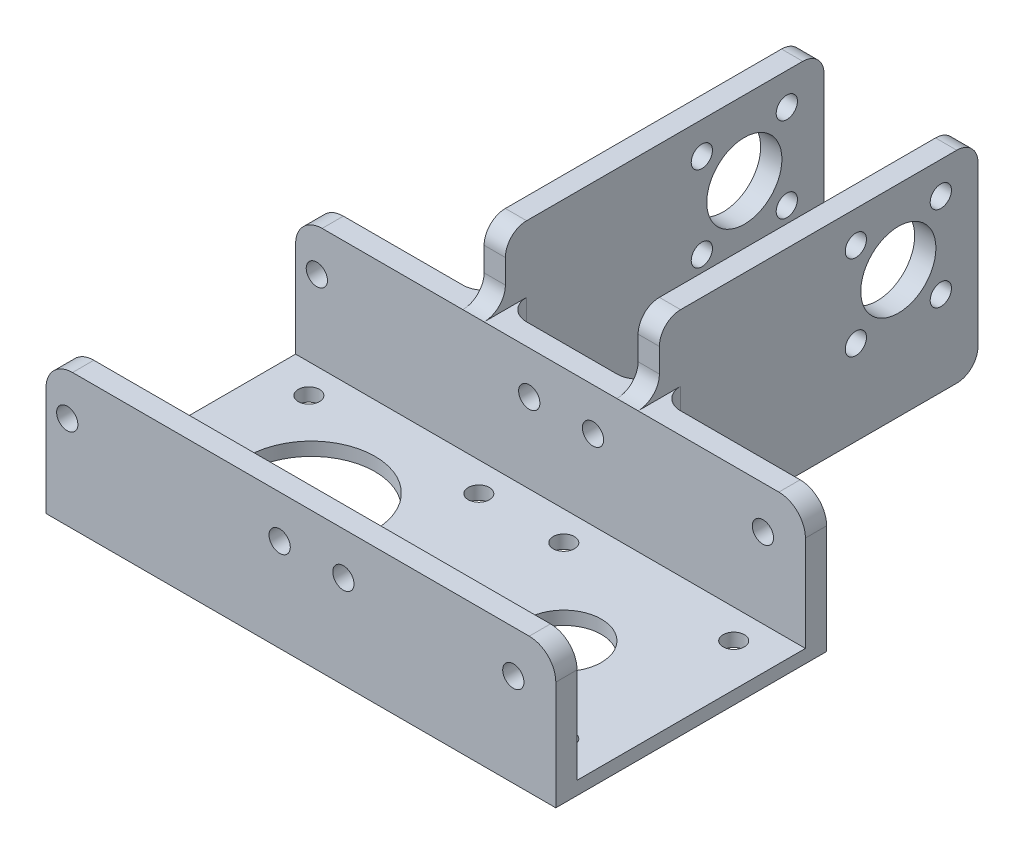
SolidWorks part; units mm, degrees
ref_plane "Front Plane" through (0, 0, 0) normal (0, 0, 1) x (1, 0, 0)
ref_plane "Top Plane" through (0, 0, 0) normal (0, 1, 0) x (1, 0, 0)
ref_plane "Right Plane" through (0, 0, 0) normal (1, 0, 0) x (0, 0, -1)
sketch "Sketch1" plane through (0, 0, 0) normal (0, 1, 0) x (1, 0, 0)
  line L1 (-41.8623, 25.1902) -> (54.1377, 25.1902)
  line L2 (-41.8623, 25.1902) -> (-41.8623, -25.8098)
  line L3 (-41.8623, -25.8098) -> (54.1377, -25.8098)
  line L4 (54.1377, 25.1902) -> (54.1377, -25.8098)
  line L5 (-41.8623, 25.1902) -> (54.1377, 25.1902)
  line L6 (-41.8623, 25.1902) -> (-41.8623, 21.1902)
  line L7 (-41.8623, 21.1902) -> (54.1377, 21.1902)
  line L9 (-41.8623, -25.8098) -> (54.1377, -25.8098)
  line L10 (-41.8623, -25.8098) -> (-41.8623, -21.8098)
  line L11 (-41.8623, -21.8098) -> (54.1377, -21.8098)
  dimension "D1" = 96
  dimension "D2" = 51
extrude "Boss-Extrude1" add sketch "Sketch1" along normal blind 2.5 contours L2 L11 L4 L7 | L11 L2 L3 L4 | L2 L7 L4 L1 region at (6.1377, 0, -23.1902) region at (6.1377, 0, 0.3098) region at (6.1377, 0, 23.8098)
extrude "Boss-Extrude2" add sketch "Sketch1<3>" along normal blind 25.5 contours L11 L2 L3 L4 | L2 L7 L4 L1 region at (6.1377, 0, -23.1902) region at (6.1377, 0, 23.8098)
sketch "Sketch1<3>" plane through (0, 0, 0) normal (0, 1, 0) x (1, 0, 0) same geometry as "Sketch1"
sketch "Sketch2" plane through (0, 0, 0) normal (0, -1, 0) x (1, 0, 0)
  line L0 (-41.8623, -25.1902) -> (54.1377, -25.1902) construction
  line L1 (-41.8623, -25.1902) -> (-41.8623, 25.8098) construction
  line L2 (54.1377, -25.1902) -> (54.1377, 25.8098) construction
  circle A0 centre (-17.8623, 0.3098) radius 7
  circle A1 centre (30.1377, 0.3098) radius 7.075
  dimension "D1" = 14
  dimension "D2" = 25.5
  dimension "D4" = 14.15
  dimension "D3" = 24
  dimension "D5" = 25.5
  dimension "D6" = 24
extrude "Cut-Extrude1" cut sketch "Sketch2" against normal blind 22
sketch "Sketch3" plane through (0, 0, 0) normal (0, -1, 0) x (1, 0, 0)
  line L0 (-41.8623, 25.8098) -> (54.1377, 25.8098) construction
  line L1 (-41.8623, -25.1902) -> (-41.8623, 25.8098) construction
  line L2 (54.1377, -25.1902) -> (54.1377, 25.8098) construction
  circle A0 centre (-33.8623, 16.3098) radius 2
  circle A1 centre (-1.8623, 16.3098) radius 2
  circle A2 centre (-1.8623, -15.6902) radius 2
  circle A3 centre (-33.8623, -15.6902) radius 2
  circle A4 centre (46.1377, 16.3098) radius 2
  circle A5 centre (14.1377, 16.3098) radius 2
  circle A6 centre (14.1377, -15.6902) radius 2
  circle A7 centre (46.1377, -15.6902) radius 2
  dimension "D1" = 4
  dimension "D6" = 4
  dimension "D2" = 9.5
  dimension "D3" = 8
  dimension "D7" = 9.5
  dimension "D8" = 8
  dimension "D4" = 2
  dimension "D5" = 2
  dimension "D9" = 2
  dimension "D10" = 2
extrude "Cut-Extrude2" cut sketch "Sketch3" against normal blind 22
sketch "Sketch4" plane through (0, 0, 25.8098) normal (0, 0, 1) x (1, 0, 0)
  line L0 (-41.8623, 0) -> (54.1377, 0) construction
  line L1 (54.1377, 25.5) -> (54.1377, 0) construction
  line L2 (-41.8623, 25.5) -> (-41.8623, 0) construction
  circle A0 centre (46.1377, 17.5) radius 2
  circle A1 centre (14.1377, 17.5) radius 2
  circle A2 centre (-37.8623, 17.5) radius 2
  circle A3 centre (2.1377, 17.5) radius 2
  dimension "D1" = 4
  dimension "D5" = 4
  dimension "D2" = 17.5
  dimension "D3" = 8
  dimension "D6" = 4
  dimension "D7" = 17.5
  dimension "D4" = 2
  dimension "D8" = 2
extrude "Cut-Extrude3" cut sketch "Sketch4" against normal blind 53
fillet "Fillet1" radius 5 4 edges at (54.1377, 25.5, 23.8098) (54.1377, 25.5, -23.1902) (-41.8623, 25.5, 23.8098) (-41.8623, 25.5, -23.1902)
sketch "Sketch6" plane through (0, 0, -25.1902) normal (0, 0, -1) x (-1, 0, 0)
  line L0 (-54.1377, 3.4956) -> (-22.6377, 3.4956)
  line L1 (-54.1377, 20.5) -> (-54.1377, 0) construction
  line L2 (41.8623, 0) -> (-54.1377, 0) construction
  line L3 (-22.6377, 0) -> (-18.6377, 0)
  line L4 (-22.6377, 0) -> (-22.6377, 38)
  line L5 (-22.6377, 38) -> (-18.6377, 38)
  line L6 (-18.6377, 0) -> (-18.6377, 38)
  line L7 (41.8623, 3.4956) -> (6.3623, 3.4956)
  line L8 (41.8623, 20.5) -> (41.8623, 0) construction
  line L10 (6.3623, 0) -> (10.3623, 0)
  line L11 (6.3623, 0) -> (6.3623, 38)
  line L12 (6.3623, 38) -> (10.3623, 38)
  line L13 (10.3623, 0) -> (10.3623, 38)
  line M15 (36.8623, 25.5) -> (-49.1377, 25.5)
  line M18 (-54.1377, 0) -> (41.8623, 0)
  dimension "D1" = 31.5
  dimension "D2" = 4
  dimension "D3" = 38
  dimension "D4" = 35.5
  dimension "D5" = 4
extrude "Boss-Extrude3" add sketch "Sketch6" along normal blind 60 contours L6 L5 L4 M15 | L6 L4 M18 M15 | L13 L7 L11 M18 | L7 L13 L11 M15 | L13 L12 L11 M15 region at (20.6377, 12.75, -25.1902) region at (20.6377, 31.75, -25.1902) region at (-8.3623, 1.7478, -25.1902) region at (-8.3623, 14.4978, -25.1902) region at (-8.3623, 31.75, -25.1902)
sketch "Sketch7" plane through (-10.3623, 0, 0) normal (-1, 0, 0) x (0, 0, 1)
  line L0 (-25.1902, 25.5) -> (-25.1902, 38) construction
  line L1 (-85.1902, 0) -> (-25.1902, 0) construction
  circle A0 centre (-70.1902, 24) radius 7.075
  circle A1 centre (-78.1902, 32) radius 2
  circle A2 centre (-62.1902, 32) radius 2
  circle A3 centre (-62.1902, 16) radius 2
  circle A4 centre (-78.1902, 16) radius 2
  dimension "D1" = 14.15
  dimension "D4" = 4
  dimension "D2" = 45
  dimension "D3" = 24
  dimension "D5" = 8
  dimension "D6" = 8
  dimension "D7" = 2
  dimension "D8" = 2
extrude "Cut-Extrude4" cut sketch "Sketch7" against normal blind 60
fillet "Fillet2" radius 4 10 edges at (-8.3623, 38, -25.1902) (20.6377, 38, -25.1902) (-8.3623, 38, -85.1902) (20.6377, 38, -85.1902) (18.6377, 12.75, -25.1902) (22.6377, 12.75, -25.1902) (20.6377, 0, -85.1902) (-8.3623, 0, -85.1902) (-6.3623, 12.75, -25.1902) (-10.3623, 12.75, -25.1902)
fillet "Fillet3" radius 4 2 edges at (20.6377, 25.5, -25.1902) (-8.3623, 25.5, -25.1902)
sketch "Sketch8" plane through (0, 0, 0) normal (0, -1, 0) x (1, 0, 0)
  circle A0 centre (-17.72, 0) radius 12
extrude "Cut-Extrude5" cut sketch "Sketch8" against normal blind 10
